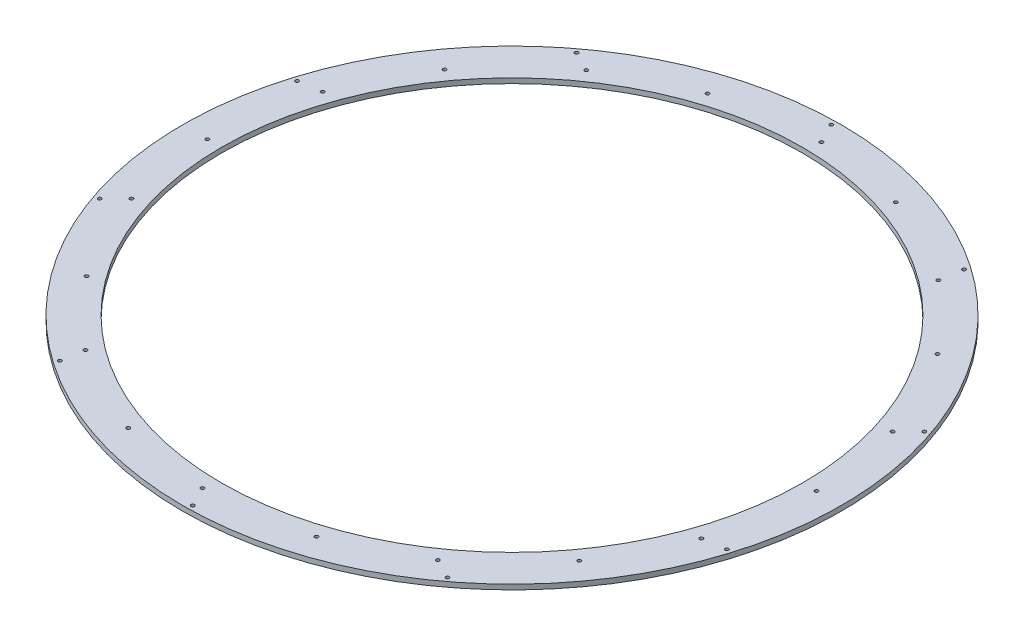
SolidWorks part; units mm, degrees
ref_plane "Front Plane" through (0, 0, 0) normal (0, 0, 1) x (1, 0, 0)
ref_plane "Top Plane" through (0, 0, 0) normal (0, 1, 0) x (1, 0, 0)
ref_plane "Right Plane" through (0, 0, 0) normal (1, 0, 0) x (0, 0, -1)
sketch "Sketch1" plane through (0, 0, 0) normal (0, 1, 0) x (1, 0, 0)
  circle A0 centre (0, 0) radius 291
  circle A1 centre (0, 0) radius 330
  dimension "D1" = 660
  dimension "D2" = 582
extrude "Boss-Extrude1" add sketch "Sketch1" against normal blind 5
sketch "Sketch2" plane through (0, 0, 0) normal (0, 1, 0) x (1, 0, 0)
  circle A5 centre (5.2385, -324.9578) radius 1.75
  circle A6 centre (94.2502, -290.0722) radius 1.75
  circle A7 centre (175.274, -249.6078) radius 1.75
  dimension "D1" = 3.5
extrude "Cut-Extrude1" cut sketch "Sketch2" against normal through all
pattern_circular "CirPattern1" count 10 over 360 about axis through (0, -5, 0) along (0, 1, 0) of "Cut-Extrude1"
